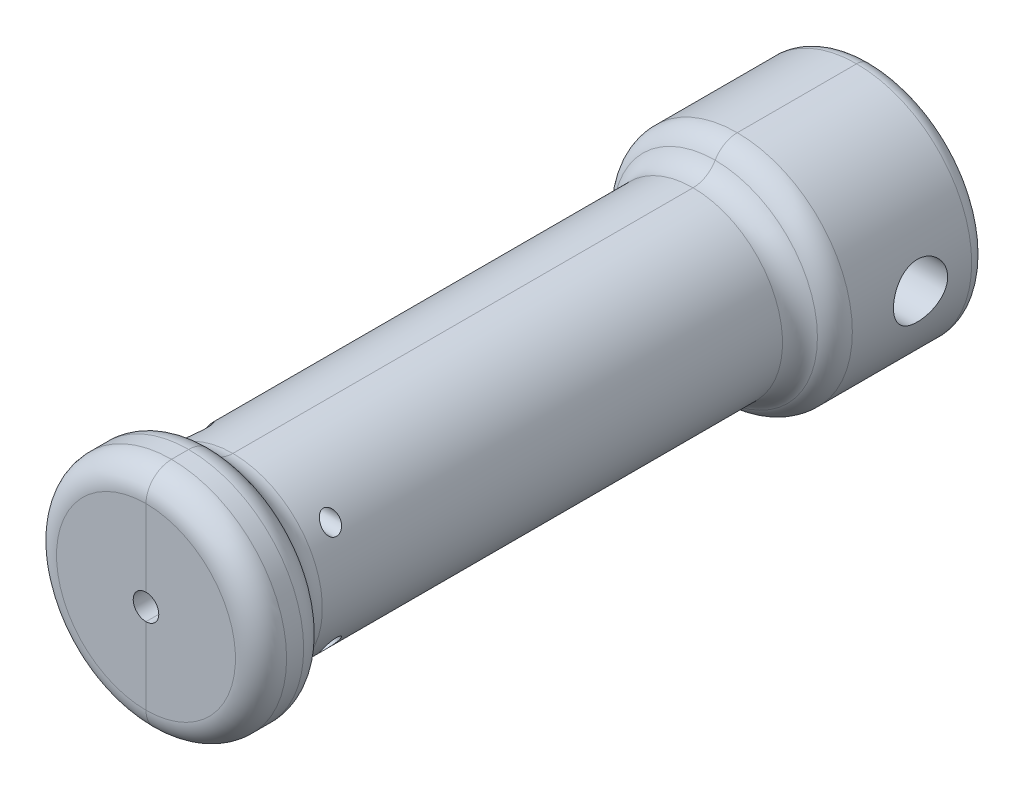
SolidWorks part; units mm, degrees
ref_plane "Plan de face" through (0, 0, 0) normal (0, 0, 1) x (1, 0, 0)
ref_plane "Plan de dessus" through (0, 0, 0) normal (0, 1, 0) x (1, 0, 0)
ref_plane "Plan de droite" through (0, 0, 0) normal (1, 0, 0) x (0, 0, -1)
ref_plane "Plan1" through (0, 0, 2) normal (0, 0, 1) x (1, 0, 0)
sketch "Esquisse2" plane through (0, 0, 2) normal (0, 0, 1) x (1, 0, 0)
  line L0 (-6.25, -6.25) -> (6.25, 6.25) construction
  circle A0 centre (0, 0) radius 22.5
  dimension "D1" = 45
extrude "Boss.-Extru.1" add sketch "Esquisse2" along normal blind 30
sketch "Esquisse3" plane through (0, 0, 32) normal (0, 0, 1) x (1, 0, 0)
  circle A0 centre (0, 0) radius 17.5
  dimension "D1" = 35
extrude "Boss.-Extru.2" add sketch "Esquisse3" along normal blind 100
sketch "Esquisse4" plane through (0, 0, 132) normal (0, 0, 1) x (1, 0, 0)
  circle A0 centre (0, 0) radius 22.5
  circle A1 centre (0, 0) radius 22.5 construction
extrude "Boss.-Extru.3" add sketch "Esquisse4" along normal blind 12
fillet "Congé2" radius 5 1 edges at (17.5, 0, 32)
fillet "Congé3" radius 5 1 edges at (17.5, 0, 132)
fillet "Congé4" radius 5 2 edges at (22.5, 0, 144) (22.5, 0, 132)
fillet "Congé5" radius 5 1 edges at (22.5, 0, 32)
sketch "Esquisse5" plane through (0, 0, 2) normal (0, 0, -1) x (-1, 0, 0)
  line L0 (-8.4, 6) -> (-8.4, -6) construction
  line L1 (-8.4, 6) -> (-8.4, -6) construction
  line L2 (-6.25, 6) -> (-6.25, -6) construction
  line L3 (-6.25, 6) -> (-6.25, -6) construction
  line L4 (-8.4, 6) -> (-6.25, 6) construction
  line L5 (-6.25, -6) -> (-8.4, -6) construction
  line L6 (-5.95, 6.3) -> (-5.95, -6.3)
  line L7 (-5.95, -6.3) -> (-8.7, -6.3)
  line L8 (-8.7, 6.3) -> (-8.7, -6.3)
  line L9 (-8.7, 6.3) -> (-5.95, 6.3)
  dimension "D1" = 0.3
extrude "Enlèv. mat.-Extru.1" cut sketch "Esquisse5" against normal blind 20
sketch "Esquisse6" plane through (0, 0, 2) normal (0, 0, -1) x (-1, 0, 0)
  line L0 (0, 0) -> (0, 22.5) construction
  circle A0 centre (0, 0) radius 22.5 construction
  circle A1 centre (0, 9.1346) radius 1.75
  dimension "D1" = 3.5
extrude "Enlèv. mat.-Extru.2" cut sketch "Esquisse6" against normal blind 50
ref_plane "Plan2" through (10, 0, 0) normal (1, 0, 0) x (0, 0, -1)
sketch "Esquisse9" plane through (0, 0, 144) normal (0, 0, 1) x (1, 0, 0)
  circle A0 centre (0, 0) radius 2.5
  dimension "D1" = 5
extrude "Enlèv. mat.-Extru.3" cut sketch "Esquisse9" against normal blind 105
sketch "Esquisse10" plane through (0, 0, 0) normal (1, 0, 0) x (0, 0, -1)
  line L0 (-127, 0) -> (-37, 0) construction
  line L1 (-91.0211, 10) -> (-61.0211, 10)
  line L2 (-91.0211, 10) -> (-91.0211, -10)
  line L3 (-91.0211, -10) -> (-61.0211, -10)
  line L4 (-61.0211, 10) -> (-61.0211, -10)
  line L5 (-91.0211, 10) -> (-61.0211, -10) construction
  line L6 (-91.0211, -10) -> (-61.0211, 10) construction
  point P0 (-76.0211, 0)
  dimension "D1" = 20
  dimension "D2" = 30
extrude "Enlèv. mat.-Extru.4" cut sketch "Esquisse10" against normal mid plane 5
fillet "Congé6" radius 3 4 edges at (0, 10, 61.0211) (0, -10, 61.0211) (0, 10, 91.0211) (0, -10, 91.0211)
sketch "Esquisse11" plane through (0, 0, 0) normal (1, 0, 0) x (0, 0, -1)
  line L1 (-51.9239, 10.6663) -> (-39.0848, 10.6663)
  line L2 (-51.9239, 10.6663) -> (-51.9239, -2.4826)
  line L3 (-51.9239, -2.4826) -> (-39.0848, -2.4826)
  line L4 (-39.0848, 10.6663) -> (-39.0848, -2.4826)
extrude "Enlèv. mat.-Extru.5" cut sketch "Esquisse11" against normal mid plane 5
sketch "Esquisse12" plane through (10, 0, 0) normal (1, 0, 0) x (0, 0, -1)
  line L0 (-2, -22.5) -> (-2, 22.5) construction
  line L1 (0, 0) -> (-148.4185, 0) construction
  circle A0 centre (-15, 0) radius 3.25
  point P5 (-41.5, 0)
  dimension "D1" = 6.5
  dimension "D2" = 13
extrude "Enlèv. mat.-Extru.6" cut sketch "Esquisse12" against normal through all and the other way through all
sketch "Esquisse14" plane through (10, 0, 0) normal (1, 0, 0) x (0, 0, -1)
  circle A0 centre (-15, 0) radius 5.3
  dimension "D1" = 10.6
extrude "Enlèv. mat.-Extru.7" cut sketch "Esquisse14" along normal through all
ref_plane "Plan3" through (-14, 0, 0) normal (1, 0, 0) x (0, 0, -1)
sketch "Esquisse15" plane through (-14, 0, 0) normal (1, 0, 0) x (0, 0, -1)
  line L1 (-20.9906, 0.4081) -> (-18.3487, -4.9839)
  line L2 (-18.3487, -4.9839) -> (-12.3582, -5.392)
  line L3 (-12.3582, -5.392) -> (-9.0094, -0.4081)
  line L4 (-9.0094, -0.4081) -> (-11.6513, 4.9839)
  line L5 (-11.6513, 4.9839) -> (-17.6418, 5.392)
  line L6 (-17.6418, 5.392) -> (-20.9906, 0.4081)
  circle A0 centre (-15, 0) radius 5.2 construction
  dimension "D1" = 10.4
extrude "Enlèv. mat.-Extru.8" cut sketch "Esquisse15" against normal through all
fillet "Congé7" radius 3 1 edges at (22.5, 0, 2)
ref_plane "Plan4" through (0, 0, 114) normal (0, 0, 1) x (1, 0, 0)
sketch "Esquisse16" plane through (0, 0, 114) normal (0, 0, 1) x (1, 0, 0)
  circle A0 centre (0, 0) radius 10
  dimension "D1" = 20
extrude "Enlèv. mat.-Extru.9" cut sketch "Esquisse16" against normal blind 8
ref_plane "Plan6" through (-7.5, 0, 0) normal (1, 0, 0) x (0, 0, -1)
sketch "Esquisse20" plane through (-7.5, 0, 0) normal (1, 0, 0) x (0, 0, -1)
  line L0 (-147.9426, 0) -> (-104.8785, 0) construction
  line L1 (-39, 0) -> (-61.0211, 0) construction
  line L2 (-127, 0) -> (-37, 0) construction
  line L3 (-144, 17.5) -> (-144, -17.5) construction
  circle A0 centre (-122, 10.3221) radius 4
  circle A1 centre (-122, -10.3221) radius 4
  dimension "D1" = 8
  dimension "D2" = 22
extrude "Enlèv. mat.-Extru.11" cut sketch "Esquisse20" against normal through all
sketch "Esquisse21" plane through (-7.5, 0, 0) normal (-1, 0, 0) x (0, 0, 1)
  circle A0 centre (122, -10.3221) radius 1.75
  circle A1 centre (122, 10.3221) radius 1.75
  dimension "D1" = 3.5
extrude "Enlèv. mat.-Extru.12" cut sketch "Esquisse21" against normal through all
split "Fractionner1" trim tools "Plan de droite" bodies to split 117 resulting bodies 118 119
